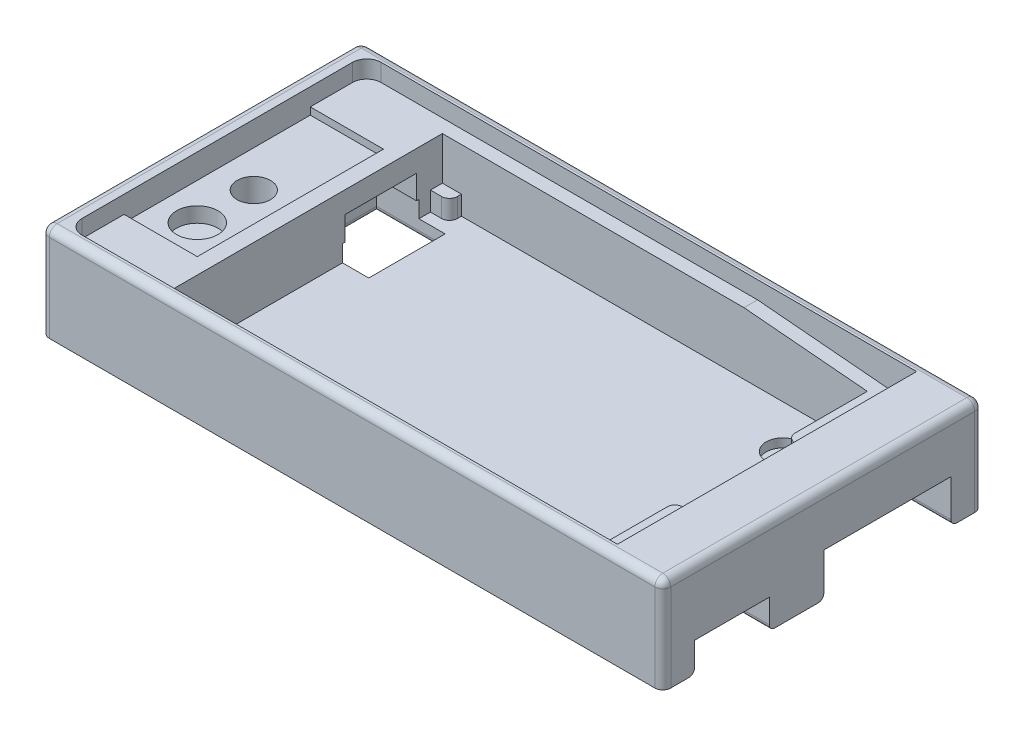
SolidWorks part; units mm, degrees
ref_plane "前视基准面" through (0, 0, 0) normal (0, 0, 1) x (1, 0, 0)
ref_plane "上视基准面" through (0, 0, 0) normal (0, 1, 0) x (1, 0, 0)
ref_plane "右视基准面" through (0, 0, 0) normal (1, 0, 0) x (0, 0, -1)
other "Configuration Table"
sketch "草图1" plane through (0, 0, 0) normal (0, 1, 0) x (1, 0, 0)
  line L0 (-39.05, 0) -> (39.05, 0) construction
  line L1 (-39.05, 20.1) -> (39.05, 20.1)
  line L2 (-39.05, 20.1) -> (-39.05, -20.1)
  line L3 (-39.05, -20.1) -> (39.05, -20.1)
  line L4 (39.05, 20.1) -> (39.05, -20.1)
  line L5 (-39.05, 20.1) -> (39.05, -20.1) construction
  line L6 (-39.05, -20.1) -> (39.05, 20.1) construction
  line L7 (-25.85, -17.1) -> (27.55, -17.1)
  line L8 (-25.85, -17.1) -> (-25.85, 17.1)
  line L9 (-25.85, 17.1) -> (27.55, 17.1)
  line L10 (27.55, -17.1) -> (27.55, 17.1)
  line L12 (32.05, 6.9973) -> (34.25, 6.9973)
  line L13 (32.05, 6.9973) -> (32.05, -6.9973)
  line L14 (32.05, -6.9973) -> (34.25, -6.9973)
  line L15 (34.25, 6.9973) -> (34.25, -6.9973)
  line L16 (-37.05, 18.8) -> (32.05, 18.8)
  line L17 (-37.05, 18.8) -> (-37.05, -18.8)
  line L18 (-37.05, -18.8) -> (32.05, -18.8)
  line L19 (32.05, 18.8) -> (32.05, -18.8)
  circle A0 centre (-32.45, 7.1) radius 2.6
  circle A1 centre (-32.45, 0) radius 2.1
  circle A2 centre (22.35, 11.6973) radius 2.1
  circle A3 centre (22.35, -11.6973) radius 2.1
  circle A4 centre (-32.45, -7.1) radius 2.6
  point P0 (0, 0)
  dimension "D1" = 4.2
  dimension "D6" = 5.2
  dimension "D2" = 5.2
  dimension "D3" = 5.4027
  dimension "D4" = 6.6
  dimension "D5" = 13
  dimension "D7" = 3
  dimension "D8" = 3
  dimension "D9" = 6.6
  dimension "D10" = 11.5
  dimension "D11" = 53.4
  dimension "D12" = 34.2
  dimension "D13" = 2.2
  dimension "D14" = 4.7
  dimension "D15" = 1.3
  dimension "D16" = 1.3
  dimension "D17" = 2
  dimension "D18" = 7
extrude "凸台-拉伸2" add sketch "草图1" along normal blind 2.2 contours L4 L1 L2 L3 L16 L19 L10 L12 L15 L14 L18 L17 | L15 L12 L10 L14 region at (0, 0, -19.2216) region at (33.15, 0, 0)
extrude "凸台-拉伸3" add sketch "草图1<4>" against normal blind 7.8 contours L19 L16 L17 L18 L7 L8 L9 A0 A1 A4 | L4 L1 L2 L3 L16 L19 L10 L12 L15 L14 L18 L17 | A4 | A0 | A1 | L15 L12 L13 L14 region at (0, 0, -19.2216) region at (33.15, 0, 0) region at (31.2633, 0, 0) region at (-32.45, 0, -7.1) region at (-32.45, 0, 0) region at (-32.45, 0, 7.1)
sketch "草图1<4>" plane through (0, 0, 0) normal (0, 1, 0) x (1, 0, 0) same geometry as "草图1"
sketch "草图2" plane through (0, 0, 0) normal (0, 1, 0) x (1, 0, 0)
  line L0 (-37.05, 18.8) -> (-37.05, -18.8) construction
  line L1 (-37.05, 11.7) -> (-27.85, 11.7)
  line L2 (-37.05, 11.7) -> (-37.05, -11.7)
  line L3 (-37.05, -11.7) -> (-27.85, -11.7)
  line L4 (-27.85, 11.7) -> (-27.85, -11.7)
  circle A0 centre (-32.45, 7.1) radius 2.6 construction
  circle A1 centre (-32.45, 7.1) radius 2.6 construction
  circle A2 centre (-32.45, -7.1) radius 2.6 construction
  circle A3 centre (-32.45, -7.1) radius 2.6 construction
  dimension "D1" = 4.6
  dimension "D2" = 4.6
  dimension "D3" = 4.6
extrude "切除-拉伸1" cut sketch "草图2" against normal blind 0.9
sketch "草图6" plane through (0, -0.9, 0) normal (0, 1, 0) x (1, 0, 0)
  circle A0 centre (-32.45, 7.1) radius 2.6 construction
  circle A1 centre (-32.45, 7.1) radius 2.6
  circle A2 centre (-32.45, -7.1) radius 2.6 construction
  circle A3 centre (-32.45, -7.1) radius 2.6
extrude "切除-拉伸2" cut sketch "草图6" against normal blind 1.9 contours A3 region at (-32.45, -0.9, 7.1)
sketch "草图7" plane through (0, -0.9, 0) normal (0, 1, 0) x (1, 0, 0)
  circle A0 centre (-32.45, 0) radius 2.1 construction
  circle A1 centre (-32.45, 0) radius 2.1
extrude "切除-拉伸3" cut sketch "草图7" against normal blind 1.1
sketch "草图8" plane through (0, -2, 0) normal (0, 1, 0) x (1, 0, 0)
  circle A0 centre (-32.45, 0) radius 1.2
  dimension "2.2" = 2.4
extrude "切除-拉伸4" cut sketch "草图8" against normal through all
sketch "草图9" plane through (0, -7.8, 0) normal (0, -1, 0) x (1, 0, 0)
  line L0 (39.05, -20.1) -> (39.05, 20.1) construction
  line L1 (-39.05, -20.1) -> (39.05, -20.1) construction
  line L2 (-39.05, -20.1) -> (-39.05, 20.1) construction
  line L3 (-39.05, 20.1) -> (39.05, 20.1) construction
  line L4 (39.05, -20.1) -> (39.05, 20.1)
  line L5 (-39.05, -20.1) -> (39.05, -20.1)
  line L6 (-39.05, -20.1) -> (-39.05, 20.1)
  line L7 (-39.05, 20.1) -> (39.05, 20.1)
extrude "凸台-拉伸4" add sketch "草图9" along normal blind 2
sketch "草图10" plane through (0, -7.8, 0) normal (0, 1, 0) x (1, 0, 0)
  circle A0 centre (22.35, -11.6973) radius 2.1 construction
  circle A1 centre (22.35, 11.6973) radius 2.1 construction
  circle A2 centre (22.35, -11.6973) radius 2.1
  circle A3 centre (22.35, 11.6973) radius 2.1
extrude "切除-拉伸5" cut sketch "草图10" against normal blind 1.1
sketch "草图11" plane through (0, -8.9, 0) normal (0, 1, 0) x (1, 0, 0)
  circle A0 centre (22.35, 11.6973) radius 1.2
  circle A1 centre (22.35, -11.6973) radius 1.2
  dimension "D1" = 2.4
  dimension "D2" = 2.4
extrude "切除-拉伸6" cut sketch "草图11" against normal through all
sketch "草图12" plane through (0, -9.8, 0) normal (0, -1, 0) x (1, 0, 0)
  line L0 (-25.85, -17.1) -> (27.55, -17.1) construction
  line L1 (-25.85, -17.1) -> (27.55, -17.1) construction
  line L7 (-30.6239, -4.85) -> (-26.1739, -4.85)
  line L8 (-30.6239, -4.85) -> (-30.6239, -13.85)
  line L9 (-30.6239, -13.85) -> (-26.1739, -13.85)
  line L10 (-26.1739, -4.85) -> (-26.1739, -13.85)
  line L11 (-30.6239, -4.85) -> (-26.1739, -13.85) construction
  line L12 (-30.6239, -13.85) -> (-26.1739, -4.85) construction
  line L13 (-28.3989, -9.35) -> (-23.0895, -9.35) construction
  line L14 (-31.1739, -4.55) -> (-26.1739, -4.55)
  line L15 (-31.1739, -4.55) -> (-31.1739, -14.15)
  line L16 (-31.1739, -14.15) -> (-26.1739, -14.15)
  line L17 (-26.1739, -4.55) -> (-26.1739, -14.15)
  point P6 (-28.3989, -9.35)
  dimension "D1" = 7.75
  dimension "D2" = 4.45
  dimension "D3" = 9
  dimension "D4" = 9.6
  dimension "D5" = 5
extrude "切除-拉伸7" cut sketch "草图12" against normal blind 7.1 contours L10 L7 L8 L9 region at (-28.3989, -9.8, -9.35)
extrude "切除-拉伸8" cut sketch "草图12<3>" against normal offset from surface (4.1 mm away) 3 contours L17 L14 L15 L16 L9 L8 L7 region at (-30.7321, -9.8, -9.35) up to face at (-28.3989, -2.7, -9.35)
sketch "草图12<3>" plane through (0, -9.8, 0) normal (0, -1, 0) x (1, 0, 0) same geometry as "草图12"
sketch "草图13" plane through (-26.1739, 0, 0) normal (-1, 0, 0) x (0, 0, 1)
  line L4 (-4.85, -2.7) -> (-13.85, -2.7)
  line L5 (-4.85, -2.7) -> (-13.85, -2.7)
  line L9 (-13.85, -2.7) -> (-13.85, -5.7)
  line L11 (-13.85, -5.7) -> (-14.15, -5.7)
  line L12 (-14.15, -9.8) -> (-4.55, -9.8)
  line L13 (-13.85, -5.7) -> (-14.15, -5.7)
  line L14 (-14.15, -5.7) -> (-14.15, -9.8)
  line L15 (-4.85, -5.7) -> (-4.85, -2.7)
  line L17 (-13.85, -2.7) -> (-13.85, -5.7)
  line L20 (-14.15, -9.8) -> (-4.55, -9.8)
  line L23 (-4.85, -5.7) -> (-4.85, -2.7)
  line L24 (-14.15, -5.7) -> (-14.15, -9.8)
  line L25 (-4.55, -9.8) -> (-4.55, -5.7)
  line L26 (-4.55, -9.8) -> (-4.55, -5.7)
  line L27 (-4.55, -5.7) -> (-4.85, -5.7)
  line L28 (-4.55, -5.7) -> (-4.85, -5.7)
  dimension "D1" = 0
extrude "切除-拉伸9" cut sketch "草图13" against normal up to surface (0.3239 mm away) up to face at (-25.85, -3.9, 0)
sketch "草图14" plane through (-25.85, 0, 0) normal (-1, 0, 0) x (0, 0, 1)
  line L4 (-14.15, -7.8) -> (-14.15, -9.8)
  line L5 (-14.15, -9.8) -> (-4.55, -9.8)
  line L7 (-4.55, -7.8) -> (-14.15, -7.8)
  line L9 (-14.15, -9.8) -> (-4.55, -9.8)
  line L11 (-4.55, -7.8) -> (-14.15, -7.8)
  line L12 (-14.15, -7.8) -> (-14.15, -9.8)
  line L14 (-4.55, -9.8) -> (-4.55, -7.8)
  line L15 (-4.55, -9.8) -> (-4.55, -7.8)
  dimension "D1" = 0
extrude "切除-拉伸10" cut sketch "草图14" against normal blind 3.3
fillet "圆角1" radius 1.8 4 edges at (32.05, 1.1, 18.8) (32.05, 1.1, -18.8) (-37.05, 1.1, -18.8) (-37.05, 1.1, 18.8)
fillet "圆角2" radius 1 8 edges at (39.05, -3.8, -20.1) (39.05, 2.2, 0) (39.05, -3.8, 20.1) (0, 2.2, -20.1) (-39.05, -3.8, -20.1) (0, 2.2, 20.1) (-39.05, 2.2, 0) (-39.05, -3.8, 20.1)
sketch "草图15" plane through (0, -7.8, 0) normal (0, 1, 0) x (1, 0, 0)
  line L0 (0, 0) -> (25.0264, 0) construction
  line L1 (-25.85, 17.1) -> (-23.45, 17.1)
  line L2 (-25.85, 17.1) -> (-25.85, 15.6)
  line L3 (-25.85, 15.6) -> (-23.45, 15.6)
  line L4 (-23.45, 17.1) -> (-23.45, 15.6)
  line L5 (-25.85, -15.6) -> (-23.45, -15.6)
  line L6 (-23.45, -17.1) -> (-23.45, -15.6)
  line L7 (-25.85, -17.1) -> (-23.45, -17.1)
  line L8 (-25.85, -17.1) -> (-25.85, -15.6)
  dimension "D1" = 2.4
  dimension "D2" = 1.5
extrude "凸台-拉伸5" add sketch "草图15" along normal blind 2.4
sketch "草图16" plane through (0, 0, 0) normal (0, 1, 0) x (1, 0, 0)
  line L0 (0, 0) -> (31.9375, 0) construction
  line L1 (27.55, -17.1) -> (27.55, 17.1) construction
  line L3 (30.2966, 8) -> (30.2966, -8)
  line L4 (32.05, 17) -> (32.05, -17) construction
  line L6 (30.2966, 10.5358) -> (30.2966, 8)
  line L7 (30.2966, -10.5358) -> (30.2966, -8)
  arc A0 (29.7669, 7.0581) -> (30.2966, 10.5358) centre (31.3381, 8.598) cw
  arc A1 (29.7669, -7.0581) -> (30.2966, -10.5358) centre (31.3381, -8.598) ccw
  ellipse E0 centre (27.55, 0) end of major axis (27.55, -8.1106) minor radius 4.5 (29.7669, -7.0581) -> (29.7669, 7.0581) ccw
  dimension "D1" = 2.2
revolve "切除-旋转1" [suppressed] cut sketch "草图16" angle 360 about L3
sketch "草图17" plane through (0, -7.8, 0) normal (0, 1, 0) x (1, 0, 0)
  circle A1 centre (-32.45, 0) radius 1.2
  circle A2 centre (-32.45, 0) radius 1.2
  dimension "D1" = 0
extrude "切除-拉伸11" cut sketch "草图17" against normal through all
sketch "草图19" plane through (0, 0, 20.1) normal (0, 0, 1) x (1, 0, 0)
  line L0 (12.05, 0) -> (33.9406, 0.2) construction
  line L1 (32.05, 2.2) -> (30.25, 2.2) construction
  line L2 (12.05, 0) -> (32.05, 2) construction
  line L6 (12.05, 0) -> (12.05, 2)
  line L11 (12.05, 0) -> (33.85, -2) construction
  line L12 (12.05, 0) -> (32.0733, -1.7518)
  line L13 (12.05, 0) -> (33.5215, -4.2678) construction
  line L14 (32.05, 2) -> (32.05, 0) construction
  line L15 (32.05, 0) -> (30.05, 0) construction
  line L17 (12.05, 2) -> (12.05, 3)
  line L18 (12.05, 3) -> (32.05, 3)
  line L19 (32.05, 2) -> (32.05, 3)
  line L20 (32.05, 2.2) -> (30.25, 2.2) construction
  line L21 (-35.25, 0) -> (30.25, 0) construction
  line L22 (-35.25, 0) -> (30.05, 0) construction
  line L23 (12.05, 2) -> (32.05, 2) construction
  line L24 (34.1416, 0) -> (32.1498, 0) construction
  line L25 (30.05, 0) -> (33.85, 0) construction
  line L26 (30.05, 0) -> (30.05, -2) construction
  line L27 (30.05, -2) -> (33.85, -2) construction
  line L28 (33.85, 0) -> (33.85, -2) construction
  line L29 (33.5215, -4.2678) -> (25.5215, -2.6777)
  line L30 (25.5215, -2.6777) -> (25.6517, -1.19)
  line L31 (33.9406, 0.2) -> (32.1489, 0.1836)
  circle A0 centre (12.05, 0) radius 20.0998 construction
  arc A3 (32.05, 2) -> (32.0733, -1.7518) centre (12.05, 0) cw
  circle A4 centre (12.05, 0) radius 21.8916 construction
  arc A5 (33.5215, -4.2678) -> (33.9406, 0.2) centre (12.05, 0) ccw
  line M8 (38.05, 1.2) -> (-38.05, 1.2)
  dimension "D1" = 2
  dimension "D2" = 20
  dimension "D3" = 5
  dimension "D4" = 2
  dimension "D5" = 20
  dimension "D6" = 6
  dimension "D7" = 1
  dimension "D8" = 1.8
  dimension "D9" = 2
  dimension "D10" = 8
  dimension "D11" = 0.2
extrude "切除-拉伸12" cut sketch "草图19" against normal up to surface (38.9 mm away) from surface contours L6 L12 M8 | L6 M8 region at (23.5042, 0.0997, 20.1) region at (22.0577, 2.0995, 20.1) up to face at (-2.5, 1.1, -18.8) starting at face at (-2.5, 1.1, 18.8)
extrude "切除-拉伸13" cut sketch "草图19<3>" against normal up to vertex (27.0973 mm away) from vertex contours L27 L12 L13 region at (30.5321, -2.2329, 20.1) up to point (34.25, 0, -6.9973) starting at point (34.25, 0, 6.9973)
sketch "草图19<3>" plane through (0, 0, 20.1) normal (0, 0, 1) x (1, 0, 0) same geometry as "草图19"
sketch "草图20" plane through (0.348, 2.3259, 0) normal (0.195, 0.9808, 0) x (0.9808, -0.195, 0)
  line L0 (0.1121, 0) -> (27.7341, 0) construction
  line L1 (27.7341, 6.9973) -> (27.7341, -6.9973) construction
  line L2 (27.7341, 6.9973) -> (27.7341, -6.9973) construction
  line L3 (27.7341, 5.3609) -> (27.7341, -5.3609)
  line L4 (27.7341, 0) -> (31.1183, 0) construction
  line L5 (31.1183, 18.8) -> (31.1183, -18.8) construction
  line L6 (29.3869, 4.2263) -> (27.7341, 5.3609) construction
  line L9 (27.7341, -5.3609) -> (27.7341, 5.3609) construction
  ellipse E0 centre (27.7341, 0) end of major axis (27.7341, 5.3609) minor radius 3.3842 (27.7341, 5.3609) -> (27.7341, -5.3609) cw
revolve "切除-旋转2" [suppressed] cut sketch "草图20" angle 360 about L3
fillet "圆角4" [suppressed] radius 1
fillet "圆角5" radius 1 2 edges at (-23.45, -6.6, 15.6) (-23.45, -6.6, -15.6)
sketch "草图21" plane through (0, -2, 0) normal (0, 1, 0) x (1, 0, 0)
  circle A1 centre (-32.45, 0) radius 2.1
  circle A2 centre (-32.45, 0) radius 2.1
  dimension "D1" = 0
extrude "切除-拉伸14" cut sketch "草图21" against normal up to surface (6.9 mm away) up to face at (22.35, -8.9, -10.4973)
sketch "草图22" plane through (0, -9.8, 0) normal (0, -1, 0) x (1, 0, 0)
  line L0 (0, 0) -> (39.25, 0) construction
  line L2 (-39.05, 14.6675) -> (-39.05, 5.2675)
  line L3 (31.15, 16.1208) -> (39.05, 16.1208)
  line L4 (31.15, 16.1208) -> (31.15, 6.7208)
  line L5 (31.15, 6.7208) -> (39.05, 6.7208)
  line L6 (39.05, 16.1208) -> (39.05, 6.7208)
  line L7 (31.15, 16.1208) -> (39.05, 6.7208) construction
  line L8 (31.15, 6.7208) -> (39.05, 16.1208) construction
  line L9 (-39.05, 14.6675) -> (-31.15, 14.6675)
  line L10 (-39.05, 5.2675) -> (-31.15, 5.2675)
  line L11 (-31.15, 14.6675) -> (-31.15, 5.2675)
  line L13 (39.05, -19.1) -> (39.05, 19.1) construction
  line L14 (-39.05, 19.1) -> (-39.05, -19.1) construction
  point P5 (35.1, 11.4208)
  dimension "D1" = 7.9
  dimension "D2" = 9.4
extrude "切除-拉伸15" cut sketch "草图22" against normal blind 3.7
sketch "草图23" plane through (0, -9.8, 0) normal (0, -1, 0) x (1, 0, 0)
  line L1 (39.05, -16.1357) -> (30.65, -16.1357)
  line L2 (39.05, -16.1357) -> (39.05, -0.1357)
  line L3 (39.05, -0.1357) -> (30.65, -0.1357)
  line L4 (30.65, -16.1357) -> (30.65, -0.1357)
  line L6 (32.0733, -18.8) -> (12.05, -18.8) construction
  line L7 (32.0733, -18.8) -> (12.05, -18.8) construction
  line L8 (39.05, -19.1) -> (39.05, 6.7208) construction
  line L9 (39.05, -19.1) -> (39.05, 6.7208) construction
  dimension "D1" = 8.4
  dimension "D2" = 16
extrude "切除-拉伸16" cut sketch "草图23" against normal blind 5.4
fillet "圆角6" radius 0.7 13 edges at (-35.1, -9.8, 5.2675) (34.85, -9.8, -16.1357) (30.65, -9.8, -8.1357) (34.85, -9.8, -0.1357) (35.1, -9.8, 6.7208) (35.1, -9.8, 16.1208) (31.15, -9.8, 11.4208) (-22.55, -9.8, -9.35) (-26.8619, -9.8, -14.15) (-31.1739, -9.8, -9.35) (-26.8619, -9.8, -4.55) (-31.15, -9.8, 9.9675) (-35.1, -9.8, 14.6675)
fillet "圆角7" radius 1 3 edges at (27.55, -2.2185, 6.9973) (27.55, -2.2185, -6.9973) (27.55, -3.0808, 0)
